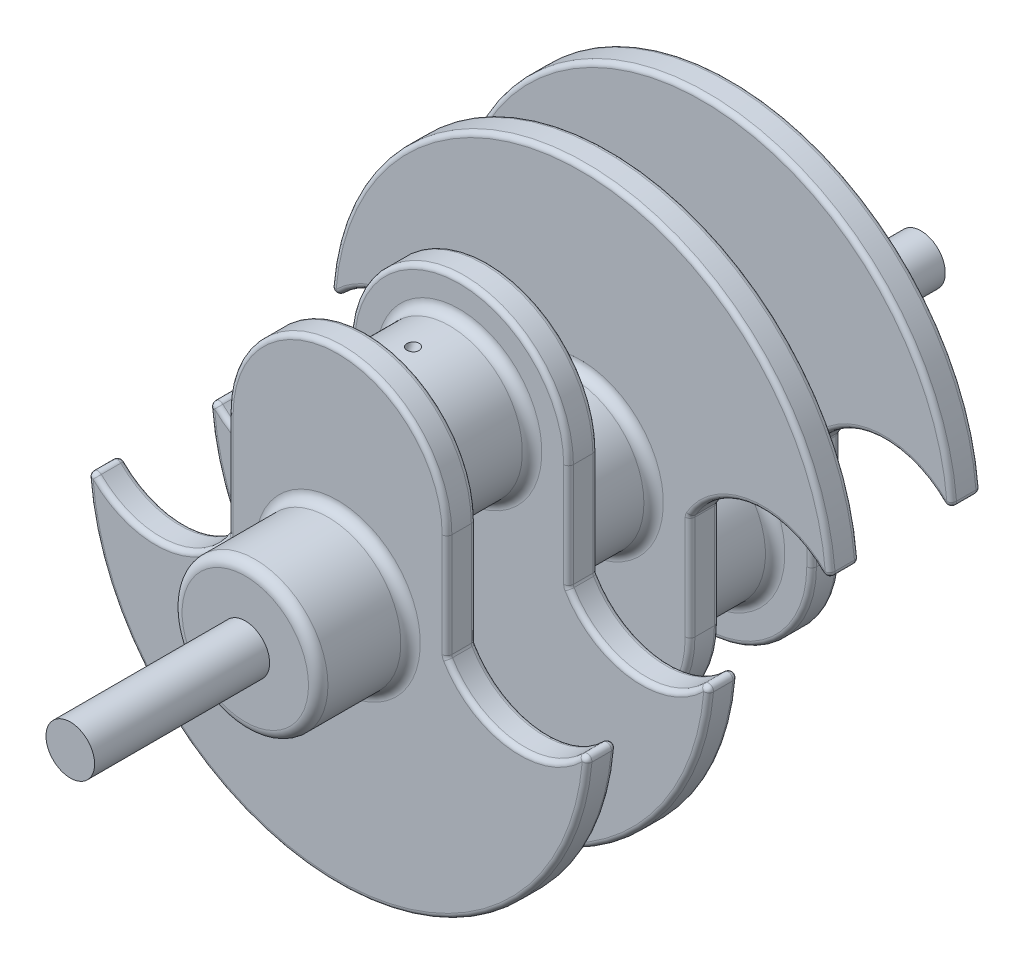
SolidWorks part; units mm, degrees
material "Low alloy steel, AISI 4340, normalized"
ref_plane "Front Plane" through (0, 0, 0) normal (0, 0, 1) x (1, 0, 0)
ref_plane "Top Plane" through (0, 0, 0) normal (0, 1, 0) x (1, 0, 0)
ref_plane "Right Plane" through (0, 0, 0) normal (1, 0, 0) x (0, 0, -1)
sketch "Sketch1" plane through (0, 0, 0) normal (0, 0, 1) x (1, 0, 0)
  circle A0 centre (0, 0) radius 30
  dimension "D1" = 30
extrude "Boss-Extrude1" add sketch "Sketch1" along normal blind 38
sketch "Sketch8" plane through (0, 0, 0) normal (0, 0, -1) x (-1, 0, 0)
  line L0 (-45, 43.2) -> (-45, 0)
  line L1 (45, 43.2) -> (45, 0)
  arc A0 (45, 43.2) -> (-45, 43.2) centre (0, 43.2) ccw
  arc A5 (-102.9647, -3) -> (102.9647, -3) centre (0, -0.3038) ccw
  arc A6 (-45, 0) -> (-102.9647, -3) centre (-74.9372, 16.949) cw
  arc A7 (45, 0) -> (102.9647, -3) centre (74.9372, 16.949) ccw
  dimension "D1" = 45
  dimension "D2" = 103
  dimension "D3" = 43.2
  dimension "D4" = 3
  dimension "D5" = 177
extrude "Boss-Extrude5" add sketch "Sketch8" along normal blind 12
sketch "Sketch2" plane through (0, 0, 38) normal (0, 0, 1) x (1, 0, 0)
  circle A0 centre (0, 0) radius 10
  dimension "D1" = 10
extrude "Boss-Extrude2" add sketch "Sketch2" along normal blind 20
sketch "Sketch9" plane through (0, 0, -12) normal (0, 0, -1) x (-1, 0, 0)
  circle A0 centre (0, 43.2) radius 30
  dimension "D2" = 30
  dimension "D1" = 43.2
extrude "Boss-Extrude6" add sketch "Sketch9" along normal blind 38
ref_plane "Plane4" through (0, 0, -100) normal (0, 0, -1) x (-1, 0, 0)
sketch "Sketch10" plane through (0, 0, -50) normal (0, 0, -1) x (-1, 0, 0)
  line L0 (-45, -43.2) -> (-45, 0)
  line L1 (45, -43.2) -> (45, 0)
  arc A0 (-45, -43.2) -> (45, -43.2) centre (0, -43.2) ccw
  arc A1 (-45, 0) -> (-102.9647, 3) centre (-74.9372, -16.949) ccw
  arc A2 (45, 0) -> (102.9647, 3) centre (74.9372, -16.949) cw
  arc A3 (-102.9647, 3) -> (102.9647, 3) centre (0, 0.3038) cw
  dimension "D1" = 45
  dimension "D4" = 3
  dimension "D5" = 177
  dimension "D3" = 103
  dimension "D2" = 43.2
extrude "Boss-Extrude7" add sketch "Sketch10" along normal blind 12 from surface starting at plane "Plane4"
ref_plane "Plane3" through (0, 0, -150) normal (0, 0, -1) x (-1, 0, 0)
sketch "Sketch12" plane through (0, 0, -150) normal (0, 0, -1) x (-1, 0, 0)
  line L2 (45, -43.2) -> (45, 0)
  line L3 (45, -43.2) -> (45, 0)
  line L4 (-45, 0) -> (-45, -43.2)
  line L5 (-45, 0) -> (-45, -43.2)
  arc A12 (-45, -43.2) -> (45, -43.2) centre (0, -43.2) ccw
  arc A13 (102.9647, 3) -> (45, 0) centre (74.9372, -16.949) ccw
  arc A14 (102.9647, 3) -> (-102.9647, 3) centre (0, 0.3038) ccw
  arc A15 (-45, 0) -> (-102.9647, 3) centre (-74.9372, -16.949) ccw
  arc A16 (-45, -43.2) -> (45, -43.2) centre (0, -43.2) ccw
  arc A17 (102.9647, 3) -> (45, 0) centre (74.9372, -16.949) ccw
  arc A18 (102.9647, 3) -> (-102.9647, 3) centre (0, 0.3038) ccw
  arc A19 (-45, 0) -> (-102.9647, 3) centre (-74.9372, -16.949) ccw
  dimension "D1" = 0
extrude "Boss-Extrude8" add sketch "Sketch12" along normal blind 12
sketch "Sketch14" plane through (0, 0, -112) normal (0, 0, -1) x (-1, 0, 0)
  circle A0 centre (0, -43.2) radius 30
  dimension "D2" = 30
  dimension "D1" = 43.2
extrude "Boss-Extrude9" add sketch "Sketch14" along normal up to next
sketch "Sketch15" plane through (0, 0, -162) normal (0, 0, -1) x (-1, 0, 0)
  circle A1 centre (0, 0) radius 30
  circle A2 centre (0, 0) radius 30
  dimension "D1" = 0
extrude "Boss-Extrude10" add sketch "Sketch15" along normal blind 38
sketch "Sketch16" plane through (0, 0, -200) normal (0, 0, -1) x (-1, 0, 0)
  circle A1 centre (0, 0) radius 10
  circle A2 centre (0, 0) radius 10
  dimension "D1" = 0
extrude "Boss-Extrude11" add sketch "Sketch16" along normal blind 40
sketch "Sketch18" plane through (0, 0, -50) normal (0, 0, -1) x (-1, 0, 0)
  line L2 (-45, 43.2) -> (-45, 0)
  line L3 (-45, 43.2) -> (-45, 0)
  line L4 (45, 0) -> (45, 43.2)
  line L5 (45, 0) -> (45, 43.2)
  arc A4 (45, 43.2) -> (-45, 43.2) centre (0, 43.2) ccw
  arc A5 (-102.9647, -3) -> (-45, 0) centre (-74.9372, 16.949) ccw
  arc A6 (-102.9647, -3) -> (102.9647, -3) centre (0, -0.3038) ccw
  arc A7 (45, 0) -> (102.9647, -3) centre (74.9372, 16.949) ccw
  arc A8 (45, 43.2) -> (-45, 43.2) centre (0, 43.2) ccw
  arc A9 (-102.9647, -3) -> (-45, 0) centre (-74.9372, 16.949) ccw
  arc A10 (-102.9647, -3) -> (102.9647, -3) centre (0, -0.3038) ccw
  arc A11 (45, 0) -> (102.9647, -3) centre (74.9372, 16.949) ccw
  dimension "D1" = 0
extrude "Boss-Extrude12" add sketch "Sketch18" along normal blind 12
sketch "Sketch19" plane through (0, 0, -62) normal (0, 0, -1) x (-1, 0, 0)
  circle A1 centre (0, 0) radius 30
  circle A2 centre (0, 0) radius 30
  dimension "D1" = 0
extrude "Boss-Extrude13" add sketch "Sketch19" along normal up to next
fillet "Fillet1" radius 2 32 edges at (0, -103.3038, -50) (-73.1591, -17.4071, -50) (-45, 21.6, -50) (45, 21.6, -50) (73.1591, -17.4071, -50) (0, -103.3038, -62) (-73.1591, -17.4071, -62) (-45, 21.6, -62) (0, 88.2, -62) (45, 21.6, -62) (73.1591, -17.4071, -62) (102.9647, -3, -56) (45, 0, -56) (-45, 0, -56) (-102.9647, -3, -56) (0, 88.2, -50) (45, 21.6, 0) (73.1591, -17.4071, 0) (0, -103.3038, 0) (-73.1591, -17.4071, 0) (-45, 21.6, 0) (0, 88.2, -12) (45, 21.6, -12) (73.1591, -17.4071, -12) (0, -103.3038, -12) (-73.1591, -17.4071, -12) (-45, 21.6, -12) (-45, 0, -6) (-102.9647, -3, -6) (102.9647, -3, -6) (45, 0, -6) (0, 88.2, 0)
fillet "Fillet2" radius 2 16 edges at (0, 103.3038, -150) (73.1591, 17.4071, -150) (45, -21.6, -150) (0, -88.2, -150) (-45, -21.6, -150) (-73.1591, 17.4071, -150) (73.1591, 17.4071, -162) (45, -21.6, -162) (0, -88.2, -162) (-45, -21.6, -162) (-73.1591, 17.4071, -162) (-102.9647, 3, -156) (-45, 0, -156) (45, 0, -156) (102.9647, 3, -156) (0, 103.3038, -162)
fillet "Fillet3" radius 2 16 edges at (45, -21.6, -100) (73.1591, 17.4071, -100) (0, 103.3038, -100) (-73.1591, 17.4071, -100) (-45, -21.6, -100) (0, -88.2, -100) (45, -21.6, -112) (73.1591, 17.4071, -112) (-73.1591, 17.4071, -112) (-45, -21.6, -112) (0, -88.2, -112) (45, 0, -106) (102.9647, 3, -106) (-102.9647, 3, -106) (-45, 0, -106) (0, 103.3038, -112)
fillet "Fillet5" radius 4 2 edges at (30, 0, 38) (30, 0, 0)
fillet "Fillet6" radius 4 2 edges at (-30, 0, -162) (-30, 0, -200)
ref_plane "Plane5" through (0, 31.75, 0) normal (0, 1, 0) x (1, 0, 0)
sketch "Sketch20" plane through (0, 0, 0) normal (1, 0, 0) x (0, 0, -1)
  line L1 (112, -73.2) -> (112, -13.2)
  line L2 (112, -73.2) -> (112, -13.2)
  dimension "D1" = 0
ref_plane "Plane6" through (0, -73.2, 0) normal (0, 1, 0) x (1, 0, 0)
sketch "Sketch21" plane through (0, 31.75, 0) normal (0, 1, 0) x (1, 0, 0)
  line L2 (-30, 196) -> (30, 196) construction
  line L3 (-30, 196) -> (-30, 166) construction
  line L4 (-30, 166) -> (30, 166) construction
  line L5 (30, 196) -> (30, 166) construction
  circle A0 centre (0, 181) radius 2.5
  point P10 (0, 196)
  point P11 (30, 181)
  dimension "D1" = 5
sketch "Sketch27" plane through (0, 0, 0) normal (0, 0, 1) x (1, 0, 0)
  line L0 (0, 73.2) -> (0, -30) construction
  circle A1 centre (0, 43.2) radius 30
  circle A2 centre (0, 43.2) radius 30 construction
  circle A3 centre (0, 0) radius 30
  circle A4 centre (0, 0) radius 30 construction
  dimension "D1" = 0
  dimension "D2" = 0
ref_plane "Plane8" through (0, 73.2, 0) normal (0, -1, 0) x (-1, 0, 0)
ref_plane "Plane9" through (0, -30, 0) normal (0, -1, 0) x (-1, 0, 0)
sketch "Sketch28" plane through (0, -30, 0) normal (0, -1, 0) x (-1, 0, 0)
  line L1 (-30, -4) -> (30, -4) construction
  line L2 (-30, -4) -> (-30, -34) construction
  line L3 (-30, -34) -> (30, -34) construction
  line L4 (30, -4) -> (30, -34) construction
  line L5 (-30, -4) -> (30, -34) construction
  line L6 (-30, -34) -> (30, -4) construction
  circle A0 centre (0, -19) radius 2.5
  point P4 (0, -19)
  dimension "D1" = 5
sketch "Sketch29" plane through (0, 73.2, 0) normal (0, -1, 0) x (-1, 0, 0)
  line L1 (30, 50) -> (-30, 50) construction
  line L2 (30, 50) -> (30, 12) construction
  line L3 (30, 12) -> (-30, 12) construction
  line L4 (-30, 50) -> (-30, 12) construction
  line L5 (30, 50) -> (-30, 12) construction
  line L6 (30, 12) -> (-30, 50) construction
  circle A0 centre (0, 31) radius 2.5
  point P4 (0, 31)
sketch "Sketch31" plane through (0, 0, 0) normal (1, 0, 0) x (0, 0, -1)
  line L0 (31, 73.2) -> (-19, -30) construction
  line L1 (50, 86.2) -> (50, 43.2) construction
  line L2 (12, 43.2) -> (12, 86.2) construction
  line L3 (50, 86.2) -> (50, 43.2) construction
  line L4 (12, 43.2) -> (12, 86.2) construction
  line L5 (50, 73.2) -> (12, 73.2) construction
ref_plane "Plane10" through (0, 73.2, -31) normal (0, -0.8999, 0.436) x (-1, 0, 0)
ref_plane "Plane11" through (0, -30, 19) normal (0, -0.8999, 0.436) x (-1, 0, 0)
combine bodies "Combine1" operation type add bodies to combine 119 109 117
fillet "Fillet7" radius 4 6 edges at (-30, 43.2, -50) (-30, 43.2, -12) (-30, 0, -62) (-30, 0, -100) (-30, -43.2, -150) (-30, -43.2, -112)
sketch "Sketch39" plane through (0, -73.2, 0) normal (0, 1, 0) x (1, 0, 0)
  line L1 (30, 146) -> (-30, 146) construction
  line L2 (30, 146) -> (30, 116) construction
  line L3 (30, 116) -> (-30, 116) construction
  line L4 (-30, 146) -> (-30, 116) construction
  line L5 (30, 146) -> (-30, 116) construction
  line L6 (30, 116) -> (-30, 146) construction
  point P4 (0, 131)
sketch "Sketch40" plane through (0, 0, 0) normal (1, 0, 0) x (0, 0, -1)
  line L0 (181, 31.75) -> (131, -73.2) construction
  line L1 (196, 31.75) -> (166, 31.75) construction
  line L2 (116, -73.2) -> (146, -73.2) construction
ref_plane "Plane12" through (0, 31.75, -181) normal (0, -0.9028, 0.4301) x (-1, 0, 0)
ref_plane "Plane13" through (0, -73.2, -131) normal (0, -0.9028, 0.4301) x (-1, 0, 0)
sketch "Sketch47" plane through (0, 73.2, -31) normal (0, -0.8999, 0.436) x (-1, 0, 0)
  ellipse E0 centre (0, 0) end of major axis (2.5, 0) minor radius 2.2498 construction
  ellipse E1 centre (0, 0) end of major axis (2.5, 0) minor radius 2.2498
sketch "Sketch48" plane through (0, -30, 19) normal (0, -0.8999, 0.436) x (-1, 0, 0)
  ellipse E0 centre (0, 0) end of major axis (2.5, 0) minor radius 2.2498 construction
  ellipse E1 centre (0, 0) end of major axis (2.5, 0) minor radius 2.2498
extrude "Cut-Extrude2" cut sketch "Sketch48" against normal through all both and the other way through all
sketch "Sketch49" plane through (0, -73.2, -131) normal (0, -0.9028, 0.4301) x (-1, 0, 0)
  circle A0 centre (0, 0) radius 2.5
  dimension "D1" = 5
extrude "Cut-Extrude3" cut sketch "Sketch49" against normal through all both and the other way through all
sketch "Sketch51" plane through (0, 0, 0) normal (1, 0, 0) x (0, 0, -1)
  line L0 (31, 73.2) -> (131, -73.2) construction
ref_plane "Plane14" through (0, 73.2, -31) normal (0, -0.8257, -0.564) x (-1, 0, 0)
sketch "Sketch53" plane through (0, 0, 58) normal (0, 0, -1) x (-1, 0, 0)
  circle A1 centre (0, 0) radius 10
  circle A2 centre (0, 0) radius 10
  dimension "D1" = 0
extrude "Boss-Extrude14" add sketch "Sketch53" against normal blind 52
equation "\"CRR\"= 43.2mm'Crank Radius"
equation "\"D1@Sketch9\"=\"CRR\""
equation "\"D1@Sketch14\"=\"CRR\""
equation "\"JR\"= 30mm'Journal Radius"
equation "\"D1@Sketch1\"=\"JR\""
equation "\"D2@Sketch9\"=\"JR\""
equation "\"D2@Sketch14\"=\"JR\""
equation "\"LT\"= 12mm'Lobe Thickness"
equation "\"D1@Boss-Extrude5\"=\"LT\""
equation "\"D1@Boss-Extrude7\"=\"LT\""
equation "\"D1@Boss-Extrude8\"=\"LT\""
equation "\"D1@Boss-Extrude12\"=\"LT\""
equation "\"D3@Sketch8\"=\"CRR\""
equation "\"D2@Sketch10\"=\"CRR\""
equation "\"JL\"= 30 + 2 * ( \"JF\" )'Journal Length"
equation "\"D1@Boss-Extrude1\"=\"JL\""
equation "\"D1@Boss-Extrude6\"=\"JL\""
equation "\"D1@Boss-Extrude10\"=\"JL\""
equation "\"LHD\"= 5mm'Lubrication Hole Diameter"
equation "\"D1@Sketch29\"=\"LHD\""
equation "\"JF\"= 4mm'Internal Journal Fillets"
equation "\"D1@Fillet7\"=\"JF\""
equation "\"D1@Fillet6\"=\"JF\""
equation "\"LR\"= 45mm'Lobe radius"
equation "\"CWR\"= 103mm'Counterweight Radius"
equation "\"D1@Sketch8\"=\"LR\""
equation "\"D2@Sketch8\"=\"CWR\""
equation "\"D3@Sketch10\"=\"CWR\""
equation "\"D1@Sketch10\"=\"LR\""
equation "\"CWA\"= 3.08923rad'Counterweight Arc"
equation "\"CWS\"= 0rad'Counterweight Slope"
equation "\"CWH\"= 3mm'Counterweight Offset"
equation "\"D5@Sketch8\"=\"CWA\""
equation "\"D5@Sketch10\"=\"CWA\""
equation "\"D4@Sketch8\"=\"CWH\""
equation "\"D4@Sketch10\"=\"CWH\""
